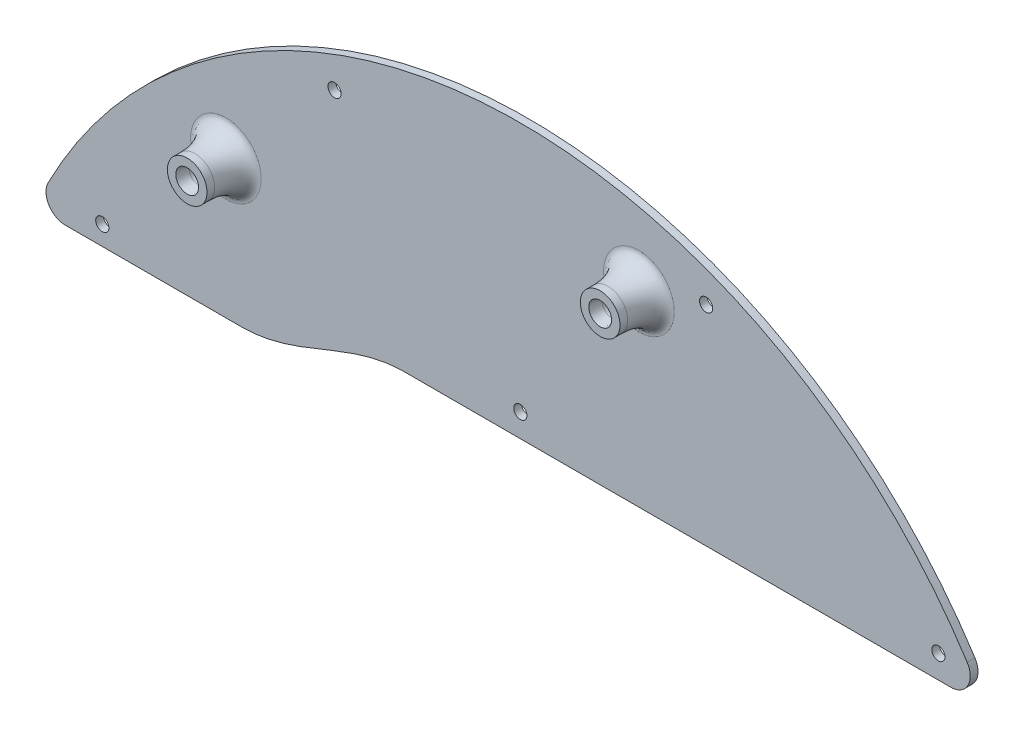
SolidWorks part; units mm, degrees
ref_plane "Ground plane" through (0, 0, 0) normal (0, 0, 1) x (1, 0, 0)
ref_plane "Medial plane" through (0, 0, 0) normal (0, 1, 0) x (1, 0, 0)
ref_plane "Frontal plane" through (0, 0, 0) normal (1, 0, 0) x (0, 0, -1)
sketch "Hole Pattern" plane through (0, 0, 0) normal (0, 0, 1) x (1, 0, 0)
  line L0 (0, 0) -> (0, 132) construction
  circle A92 centre (-108, 60) radius 1.5437
  circle A93 centre (-96, 60) radius 1.5437
  circle A94 centre (-84, 60) radius 1.5437
  circle A95 centre (-72, 60) radius 1.5437
  circle A96 centre (-60, 60) radius 1.5437
  circle A97 centre (-48, 60) radius 1.5437
  circle A98 centre (-36, 60) radius 1.5437
  circle A99 centre (-24, 60) radius 1.5437
  circle A100 centre (-12, 60) radius 1.5437
  circle A101 centre (0, 60) radius 1.5437
  circle A102 centre (12, 60) radius 1.5437
  circle A103 centre (24, 60) radius 1.5437
  circle A104 centre (36, 60) radius 1.5437
  circle A105 centre (48, 60) radius 1.5437
  circle A106 centre (96, 60) radius 1.5437
  circle A107 centre (108, 60) radius 1.5437
  circle A108 centre (-96, 72) radius 1.5437
  circle A109 centre (-84, 72) radius 1.5437
  circle A110 centre (-72, 72) radius 1.5437
  circle A111 centre (-60, 72) radius 1.5437
  circle A112 centre (-48, 72) radius 1.5437
  circle A113 centre (-36, 72) radius 1.5437
  circle A114 centre (-24, 72) radius 1.5437
  circle A115 centre (-12, 72) radius 1.5437
  circle A116 centre (0, 72) radius 1.5437
  circle A117 centre (12, 72) radius 1.5437
  circle A118 centre (24, 72) radius 1.5437
  circle A119 centre (36, 72) radius 1.5437
  circle A120 centre (48, 72) radius 1.5437
  circle A121 centre (60, 72) radius 1.5437
  circle A122 centre (72, 72) radius 1.5437
  circle A123 centre (84, 72) radius 1.5437
  circle A124 centre (96, 72) radius 1.5437
  circle A125 centre (108, 72) radius 1.5437
  circle A126 centre (-96, 84) radius 1.5437
  circle A127 centre (-84, 84) radius 1.5437
  circle A128 centre (-72, 84) radius 1.5437
  circle A129 centre (-60, 84) radius 1.5437
  circle A130 centre (-48, 84) radius 1.5437
  circle A131 centre (-36, 84) radius 1.5437
  circle A132 centre (-24, 84) radius 1.5437
  circle A133 centre (-12, 84) radius 1.5437
  circle A134 centre (0, 84) radius 1.5437
  circle A135 centre (12, 84) radius 1.5437
  circle A136 centre (24, 84) radius 1.5437
  circle A137 centre (36, 84) radius 1.5437
  circle A138 centre (48, 84) radius 1.5437
  circle A139 centre (60, 84) radius 1.5437
  circle A140 centre (72, 84) radius 1.5437
  circle A141 centre (84, 84) radius 1.5437
  circle A142 centre (96, 84) radius 1.5437
  circle A143 centre (-84, 96) radius 1.5437
  circle A144 centre (-72, 96) radius 1.5437
  circle A145 centre (-60, 96) radius 1.5437
  circle A146 centre (-48, 96) radius 1.5437
  circle A147 centre (-36, 96) radius 1.5437
  circle A148 centre (-24, 96) radius 1.5437
  circle A149 centre (-12, 96) radius 1.5437
  circle A150 centre (0, 96) radius 1.5437
  circle A151 centre (12, 96) radius 1.5437
  circle A152 centre (24, 96) radius 1.5437
  circle A153 centre (36, 96) radius 1.5437
  circle A154 centre (48, 96) radius 1.5437
  circle A155 centre (60, 96) radius 1.5437
  circle A156 centre (72, 96) radius 1.5437
  circle A157 centre (84, 96) radius 1.5437
  circle A158 centre (-72, 108) radius 1.5437
  circle A159 centre (-60, 108) radius 1.5437
  circle A160 centre (-48, 108) radius 1.5437
  circle A161 centre (-36, 108) radius 1.5437
  circle A162 centre (-24, 108) radius 1.5437
  circle A163 centre (-12, 108) radius 1.5437
  circle A164 centre (0, 108) radius 1.5437
  circle A165 centre (12, 108) radius 1.5437
  circle A166 centre (24, 108) radius 1.5437
  circle A167 centre (36, 108) radius 1.5437
  circle A168 centre (48, 108) radius 1.5437
  circle A169 centre (60, 108) radius 1.5437
  circle A170 centre (72, 108) radius 1.5437
  circle A171 centre (-48, 120) radius 1.5437
  circle A172 centre (-36, 120) radius 1.5437
  circle A173 centre (-24, 120) radius 1.5437
  circle A174 centre (-12, 120) radius 1.5437
  circle A175 centre (0, 120) radius 1.5437
  circle A176 centre (12, 120) radius 1.5437
  circle A177 centre (24, 120) radius 1.5437
  circle A178 centre (36, 120) radius 1.5437
  circle A179 centre (48, 120) radius 1.5437
  circle A180 centre (-12, 132) radius 1.5437
  circle A181 centre (0, 132) radius 1.5437
  circle A182 centre (12, 132) radius 1.5437
  circle A183 centre (-108, 72) radius 1.5437
sketch "Base Outline" plane through (0, 0, 0) normal (0, 0, 1) x (1, 0, 0)
  line L3 (-125.4751, 55) -> (-40.5641, 55)
  line L4 (-40.5641, 55) -> (-40.5641, 66)
  line L5 (120.0542, 66) -> (-40.5641, 66)
  circle A1 centre (0, 0) radius 137 construction
  arc A2 (120.0542, 66) -> (-125.4751, 55) centre (0, 0) ccw
  dimension "D1" = 274
  dimension "D2" = 11
  dimension "D3" = 6
sketch "TTB4 Standard Top Plate Outline" plane through (0, 0, 0) normal (0, 0, 1) x (1, 0, 0)
  line L2 (115, -70.7107) -> (115, 70.7107)
  circle A0 centre (-76.0694, -90.6262) radius 2.25
  arc A2 (115, 70.7107) -> (115, -70.7107) centre (0, 0) ccw
  circle A3 centre (30.6294, -114.2808) radius 2.25
  circle A4 centre (30.6294, 114.3106) radius 2.25
  circle A5 centre (-76.0694, 90.656) radius 2.25
sketch "Sketch2" plane through (0, 0, 0) normal (0, 0, 1) x (1, 0, 0)
  line L0 (-125.4751, 55) -> (-40.5641, 55) construction
  line L1 (120.0542, 66) -> (-40.5641, 66) construction
  line L2 (111.2396, 66) -> (-29.6958, 66)
  line L3 (-72.1027, 55) -> (-117.5419, 55)
  arc A0 (-121.9866, 62.2901) -> (115.4441, 73.7059) centre (0.0258, -0.575) cw
  circle A1 centre (0, 0) radius 137 construction
  arc A2 (-121.9866, 62.2901) -> (-117.5419, 55) centre (-117.5419, 60) ccw
  arc A3 (115.4441, 73.7059) -> (111.2396, 66) centre (111.2396, 71) cw
  spline S0 degree 3 poles (-72.1027, 55) (-57.0449, 55) (-44.8946, 66) (-29.6958, 66) knots 0 0 0 0 1 1 1 1
  point P21 (-125.4751, 55)
  point P24 (120.0542, 66)
  dimension "D1" = 5
extrude "Plate" add sketch "Sketch2" along normal blind 2
hole_wizard "Mounting Holes (M3)" positions "Sketch4" profile "Sketch5" hole size "M3" standard "ANSI Metric" end condition through all
sketch "Sketch4" plane through (0, 0, 2) normal (0, 0, 1) x (1, 0, 0)
  point P0 (108, 72)
  point P3 (48, 120)
  point P6 (-48, 120)
  point P9 (-108, 60)
  point P25 (0, 72)
sketch "Sketch5" plane through (108, 72, 2) normal (1, 0, 0) x (0, -1, 0)
  line L0 (0, 0) -> (0, 2)
  line L1 (0, 2) -> (1.7, 2)
  line L2 (1.7, 2) -> (1.7, 0)
  line L5 (1.7, 0) -> (0, 0)
  line L11 (0, -6.35) -> (0, 107.95) construction
  dimension "Thru Hole Dia." = 3.4
  dimension "Thru Hole Depth" = 2
sketch "Sketch7" plane through (0, 0, 2) normal (0, 0, 1) x (1, 0, 0)
  line L1 (-71.4506, 90.656) -> (-73.76, 94.656) construction
  line L2 (-73.76, 94.656) -> (-78.3789, 94.656) construction
  line L3 (-78.3789, 94.656) -> (-80.6883, 90.656) construction
  line L4 (-80.6883, 90.656) -> (-78.3789, 86.656) construction
  line L5 (-78.3789, 86.656) -> (-73.76, 86.656) construction
  line L6 (-73.76, 86.656) -> (-71.4506, 90.656) construction
  circle A0 centre (-76.0694, 90.656) radius 4 construction
  circle A1 centre (-76.0694, 90.656) radius 5.1188
  circle A2 centre (-76.0694, 90.656) radius 4.6188 construction
  circle A3 centre (30.6294, 114.3106) radius 5.1188
  dimension "D1" = 8
  dimension "D2" = 0.5
extrude "Boss-Extrude2" add sketch "Sketch7" along normal blind 10
hole_wizard "#8 (0.199) Diameter Hole1" positions "Sketch8" profile "Sketch9" hole size "#8" standard "ANSI Inch"
sketch "Sketch8" plane through (0, 0, 12) normal (0, 0, 1) x (1, 0, 0)
  point P0 (-76.0694, 90.656)
  point P3 (30.6294, 114.3106)
sketch "Sketch9" plane through (-76.0694, 90.656, 12) normal (1, 0, 0) x (0, -1, 0)
  line L0 (0, 0) -> (0, 11.5176)
  line L1 (0, 11.5176) -> (2.5273, 9.999)
  line L2 (2.5273, 9.999) -> (2.5273, 0)
  line L5 (2.5273, 0) -> (0, 0)
  line L10 (0, 11.5176) -> (-2.5273, 9.999) construction
  line L11 (0, -6.35) -> (0, 107.95) construction
  dimension "Hole Dia." = 5.0546
  dimension "Hole Depth" = 9.999
  dimension "Drill Angle" = 118
fillet "Fillet1" radius 8 2 edges at (25.5106, 114.3106, 2) (-81.1883, 90.656, 2) second distance 4 first distance on face at (35.7482, 114.3106, 12) first distance on face at (-70.9506, 90.656, 12)
chamfer "Chamfer2" distance 3 angle 8 2 edges at (33.1567, 114.3106, 12) (-73.5421, 90.656, 12) first distance on face at (33.1567, 114.3106, 2) first distance on face at (-73.5421, 90.656, 2)
